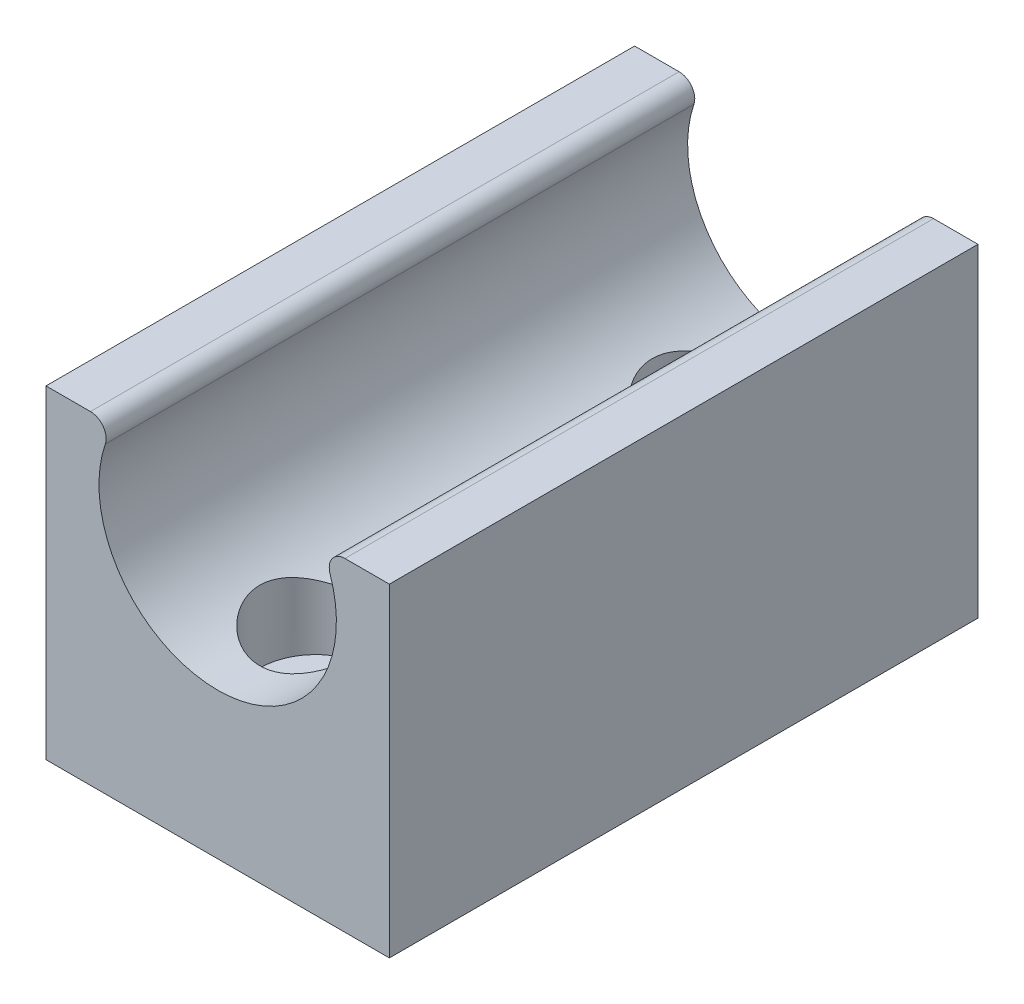
SolidWorks part; units mm, degrees
ref_plane "Front Plane" through (0, 0, 0) normal (0, 0, 1) x (1, 0, 0)
ref_plane "Top Plane" through (0, 0, 0) normal (0, 1, 0) x (1, 0, 0)
ref_plane "Right Plane" through (0, 0, 0) normal (1, 0, 0) x (0, 0, -1)
sketch "Sketch1" plane through (0, 0, 0) normal (0, 0, 1) x (1, 0, 0)
  line L0 (-5.25, 8.25) -> (-8.75, 8.25)
  line L1 (8.75, -8.25) -> (-8.75, -8.25)
  line L2 (8.75, -8.25) -> (8.75, 8.25)
  line L3 (8.75, 8.25) -> (5.25, 8.25)
  line L4 (-8.75, -8.25) -> (-8.75, 8.25)
  line L5 (8.75, -8.25) -> (-8.75, 8.25) construction
  line L6 (8.75, 8.25) -> (-8.75, -8.25) construction
  arc A0 (-5.25, 8.25) -> (5.25, 8.25) centre (0, 5.2433) ccw
  point P0 (0, 0)
  dimension "D1" = 12.1
  dimension "D2" = 3.5
  dimension "D3" = 17.5
  dimension "D4" = 16.5
extrude "Boss-Extrude1" add sketch "Sketch1" along normal blind 30
fillet "Fillet1" radius 0.8 2 edges at (5.25, 8.25, 15) (-5.25, 8.25, 15)
sketch "Sketch3" plane through (0, 8.25, 0) normal (0, 1, 0) x (1, 0, 0)
  line L0 (6.05, 0) -> (-6.05, 0) construction
  line L1 (-6.05, -30) -> (6.05, -30) construction
  circle A0 centre (0, -5) radius 2.85
  circle A1 centre (0, -25) radius 2.85
  dimension "D1" = 5.7
  dimension "D2" = 5
  dimension "D3" = 5
extrude "Cut-Extrude1" cut sketch "Sketch3" against normal blind 12
sketch "Sketch4" plane through (0, 8.25, 0) normal (0, 1, 0) x (1, 0, 0)
  circle A0 centre (0, -5) radius 1.55
  circle A1 centre (0, -25) radius 1.55
  dimension "D1" = 3.1
  dimension "D2" = 3.1
extrude "Cut-Extrude2" cut sketch "Sketch4" against normal through all
